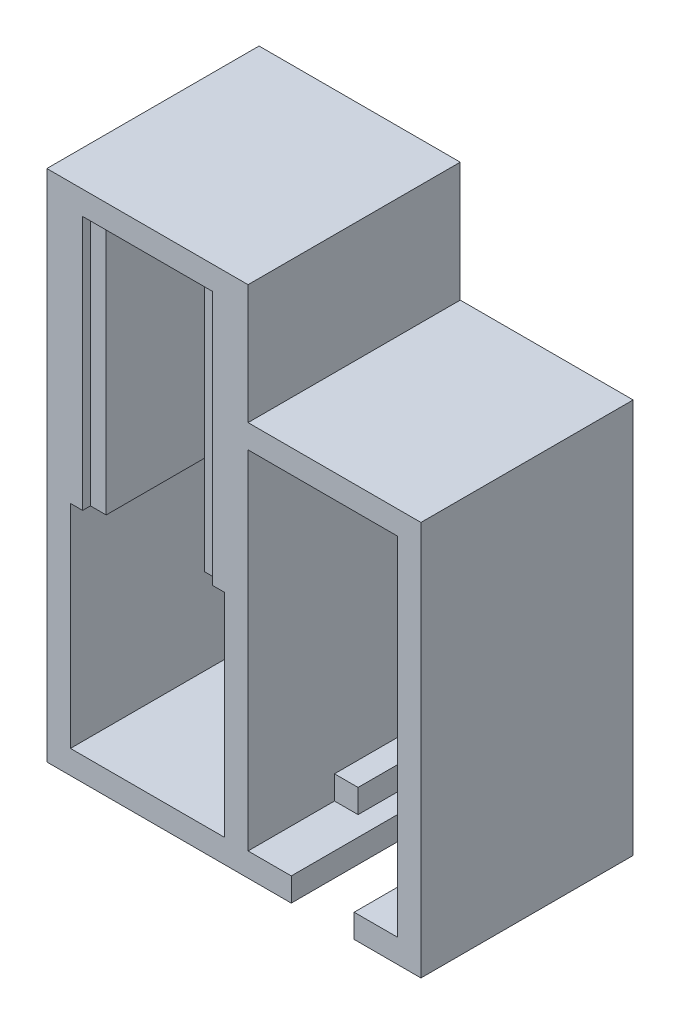
SolidWorks part; units mm, degrees
ref_plane "Front Plane" through (0, 0, 0) normal (0, 0, 1) x (1, 0, 0)
ref_plane "Top Plane" through (0, 0, 0) normal (0, 1, 0) x (1, 0, 0)
ref_plane "Right Plane" through (0, 0, 0) normal (1, 0, 0) x (0, 0, -1)
sketch "Sketch1" plane through (0, 0, 0) normal (0, 0, 1) x (1, 0, 0)
  line L0 (0, 0) -> (19, 0)
  line L1 (19, 0) -> (16, 0)
  line L2 (0, 0) -> (3, 0)
  line L3 (3, 0) -> (3, 3)
  line L4 (3, 3) -> (0, 3)
  line L5 (0, 3) -> (0, 0)
  line L6 (19, 0) -> (19, 3)
  line L7 (19, 3) -> (16, 3)
  line L8 (16, 3) -> (16, 0)
  line L9 (19, 0) -> (19, 44.2)
  line L10 (19, 44.2) -> (14, 44.2)
  line L11 (14, 44.2) -> (14, 41.2)
  line L12 (14, 41.2) -> (19, 41.2)
  line L13 (14, 44.2) -> (0, 44.2)
  line L14 (0, 44.2) -> (0, 41.2)
  line L15 (0, 41.2) -> (5, 41.2)
  line L16 (5, 41.2) -> (5, 44.2)
  line L17 (0, 41.2) -> (0, 3)
  line L18 (19, 0) -> (22, 0)
  line L19 (22, 0) -> (22, -3)
  line L20 (22, -3) -> (0, -3)
  line L21 (22, 0) -> (22, 44.2)
  line L22 (22, 44.2) -> (22, 47.2)
  line L23 (22, 47.2) -> (0, 47.2)
  line L24 (0, 47.2) -> (0, 44.2)
  line L25 (0, -3) -> (-25.6, -3)
  line L26 (0, 0) -> (-3, 0)
  line L27 (-3, 0) -> (-3, 27)
  line L28 (-3, 27) -> (-4.55, 27)
  line L29 (-4.55, 27) -> (-4.55, 59.4)
  line L30 (-4.55, 59.4) -> (-21.05, 59.4)
  line L31 (-21.05, 59.4) -> (-21.05, 27)
  line L32 (-21.05, 27) -> (-22.6, 27)
  line L33 (-25.6, -3) -> (-25.6, 27)
  line L34 (-25.6, 27) -> (-22.6, 27)
  line L35 (-22.6, 27) -> (-22.6, 0)
  line L36 (-22.6, 0) -> (-3, 0)
  line L37 (-25.6, 27) -> (-25.6, 59.4)
  line L38 (-25.6, 59.4) -> (-25.6, 62.4)
  line L39 (-25.6, 62.4) -> (-4.55, 62.4)
  line L40 (-4.55, 62.4) -> (0, 62.4)
  line L41 (0, 62.4) -> (0, 47.2)
  line L42 (-21.05, 27) -> (-19.05, 27)
  line L43 (-19.05, 27) -> (-19.05, 59.4)
  line L44 (-4.55, 27) -> (-6.55, 27)
  line L45 (-6.55, 27) -> (-6.55, 59.4)
  line L46 (0, -3) -> (5.5, -3)
  line L47 (5.5, -3) -> (5.5, 0)
  line L48 (5.5, 0) -> (13.5, 0)
  line L49 (13.5, 0) -> (13.5, -3)
  dimension "D1" = 19
  dimension "D2" = 3
  dimension "D3" = 3
  dimension "D4" = 22
  dimension "D5" = 25.6
extrude "Boss-Extrude1" add sketch "Sketch1" along normal blind 3 contours L20 L47 L0 L26 L36 L35 L34 L33 L25 | L41 L40 L39 L38 L37 L34 L32 L31 L30 L29 L28 L27 L26 L5 L17 L14 L24 | L42 L43 L30 L31 | L44 L45 L30 L43 L42 L32 L35 L36 L27 L28 | L15 L16 L13 L14 | L23 L24 L13 L10 L9 L6 L18 L21 L22 | L11 L12 L9 L10 | L15 L17 L4 L3 L0 L8 L7 L9 L12 L11 L13 L16 | L7 L8 L0 L6 | L0 L49 L20 L19 L18 | L4 L5 L0 L3 | L49 L0 L47 L20 | L45 L44 L29 L30 region at (1.5, 1.5, 0) region at (-1.5, 0.6745, 0) region at (1.5, -0.4321, 0) region at (9.5, 21.7878, 0) region at (-12.8, 26.3757, 0) region at (9.5, -1.5, 0) region at (2.5, 42.7, 0) region at (17.75, -1.5, 0) region at (0.5208, 45.7, 0) region at (-5.55, 43.2, 0) region at (17.5, 1.5, 0) region at (-20.05, 43.2, 0) region at (16.5, 42.7, 0)
extrude "Boss-Extrude2" add sketch "Sketch1<3>" along normal blind 27 contours L41 L40 L39 L38 L37 L34 L32 L31 L30 L29 L28 L27 L26 L5 L17 L14 L24 | L20 L47 L0 L26 L36 L35 L34 L33 L25 | L0 L49 L20 L19 L18 | L23 L24 L13 L10 L9 L6 L18 L21 L22 region at (-1.5, 0.6745, 0) region at (1.5, -0.4321, 0) region at (17.75, -1.5, 0) region at (0.5208, 45.7, 0)
sketch "Sketch1<3>" plane through (0, 0, 0) normal (0, 0, 1) x (1, 0, 0) same geometry as "Sketch1"
extrude "Boss-Extrude3" add sketch "Sketch1<4>" along normal blind 16 contours L15 L16 L13 L14 | L11 L12 L9 L10 | L7 L8 L0 L6 | L4 L5 L0 L3 region at (1.5, 1.5, 0) region at (2.5, 42.7, 0) region at (17.5, 1.5, 0) region at (16.5, 42.7, 0)
sketch "Sketch1<4>" plane through (0, 0, 0) normal (0, 0, 1) x (1, 0, 0) same geometry as "Sketch1"
extrude "Boss-Extrude4" add sketch "Sketch1<5>" along normal blind 11 contours L49 L0 L47 L20 region at (9.5, -1.5, 0)
sketch "Sketch1<5>" plane through (0, 0, 0) normal (0, 0, 1) x (1, 0, 0) same geometry as "Sketch1"
extrude "Boss-Extrude5" add sketch "Sketch1<6>" along normal blind 26 contours L45 L44 L29 L30 | L42 L43 L30 L31 region at (-5.55, 43.2, 0) region at (-20.05, 43.2, 0)
sketch "Sketch1<6>" plane through (0, 0, 0) normal (0, 0, 1) x (1, 0, 0) same geometry as "Sketch1"
